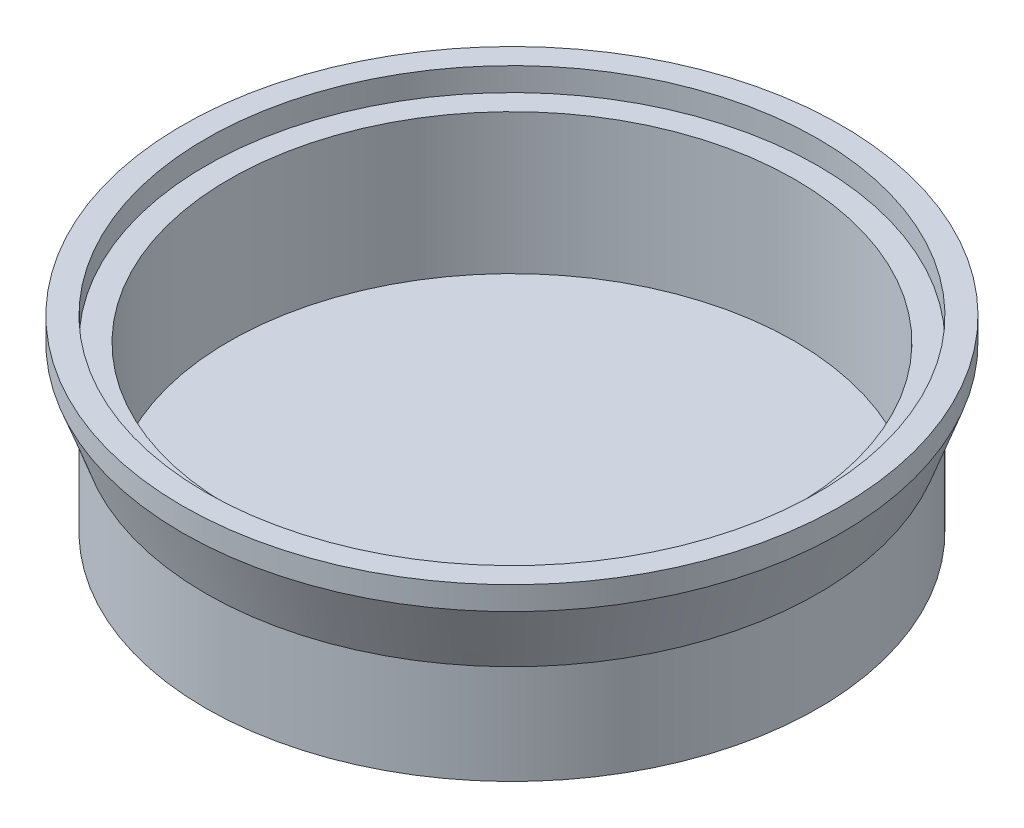
SolidWorks part; units mm, degrees
ref_plane "Front Plane" through (0, 0, 0) normal (0, 0, 1) x (1, 0, 0)
ref_plane "Top Plane" through (0, 0, 0) normal (0, 1, 0) x (1, 0, 0)
ref_plane "Right Plane" through (0, 0, 0) normal (1, 0, 0) x (0, 0, -1)
sketch "Sketch1" plane through (0, 0, 0) normal (0, 0, 1) x (1, 0, 0)
  line L0 (0, 93.6855) -> (0, -90.7684) construction
  line L1 (151.4677, 0) -> (-113.8812, 0) construction
  line L2 (0, 0) -> (-65.5, 0)
  line L3 (-65.5, 0) -> (-65.5, 21.2626)
  line L6 (-70.5, 40) -> (-65.5, 40)
  line L7 (-65.5, 40) -> (-65.5, 35)
  line L8 (-65.5, 35) -> (-60.5, 35)
  line L9 (-60.5, 35) -> (-60.5, 5)
  line L10 (-60.5, 5) -> (0, 5)
  line L11 (0, 5) -> (0, 0)
  line L13 (-70.5, 40) -> (-70.5, 35)
  line L14 (-70.5, 35) -> (-65.5, 21.2626)
  dimension "D1" = 5
  dimension "D2" = 5
  dimension "D3" = 10
  dimension "D4" = 5
  dimension "D5" = 20
  dimension "D6" = 40
  dimension "D7" = 5
  dimension "D8" = 65.5
revolve "Revolve1" add sketch "Sketch1" angle 360 about L11 region at (-32.75, 0.8106, 0)
